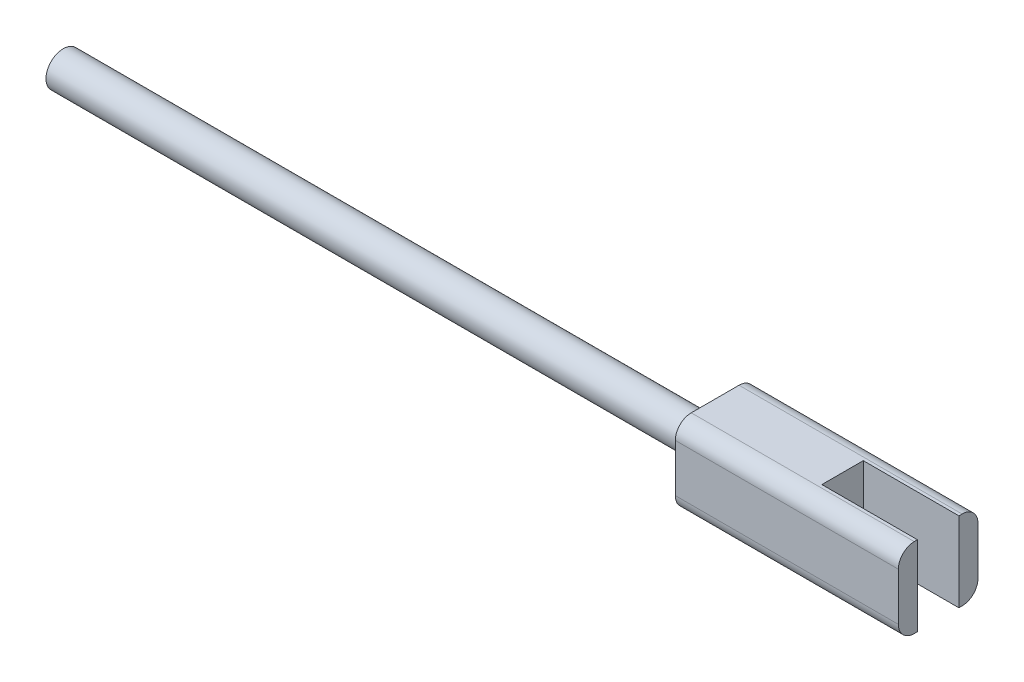
SolidWorks part; units mm, degrees
ref_plane "Front Plane" through (0, 0, 0) normal (0, 0, 1) x (1, 0, 0)
ref_plane "Top Plane" through (0, 0, 0) normal (0, 1, 0) x (1, 0, 0)
ref_plane "Right Plane" through (0, 0, 0) normal (1, 0, 0) x (0, 0, -1)
sketch "Sketch1" plane through (0, 0, 0) normal (1, 0, 0) x (0, 0, -1)
  circle A0 centre (0, 0) radius 1.09
extrude "Boss-Extrude1" add sketch "Sketch1" along normal blind 42.913
ref_plane "Plane1" through (40.913, 0, 0) normal (1, 0, 0) x (0, 0, -1)
sketch "Sketch2" plane through (40.913, 0, 0) normal (1, 0, 0) x (0, 0, -1)
  line L0 (-1.5, -2.5) -> (1.5, -2.5)
  line L1 (2.5, -1.5) -> (2.5, 1.5)
  line L2 (1.5, 2.5) -> (-1.5, 2.5)
  line L3 (-2.5, 1.5) -> (-2.5, -1.5)
  arc A0 (1.5, -2.5) -> (2.5, -1.5) centre (1.5, -1.5) ccw
  arc A1 (2.5, 1.5) -> (1.5, 2.5) centre (1.5, 1.5) ccw
  arc A2 (-1.5, 2.5) -> (-2.5, 1.5) centre (-1.5, 1.5) ccw
  arc A3 (-2.5, -1.5) -> (-1.5, -2.5) centre (-1.5, -1.5) ccw
extrude "Boss-Extrude2" add sketch "Sketch2" along normal blind 14
sketch "Sketch3" plane through (0, 0, 0) normal (0, 1, 0) x (1, 0, 0)
  line L0 (48.913, 1.3) -> (55.913, 1.3)
  line L1 (55.913, 1.3) -> (55.913, -1.3)
  line L2 (55.913, -1.3) -> (48.913, -1.3)
  line L3 (48.913, -1.3) -> (48.913, 1.3)
extrude "Cut-Extrude1" cut sketch "Sketch3" against normal through all and the other way through all
